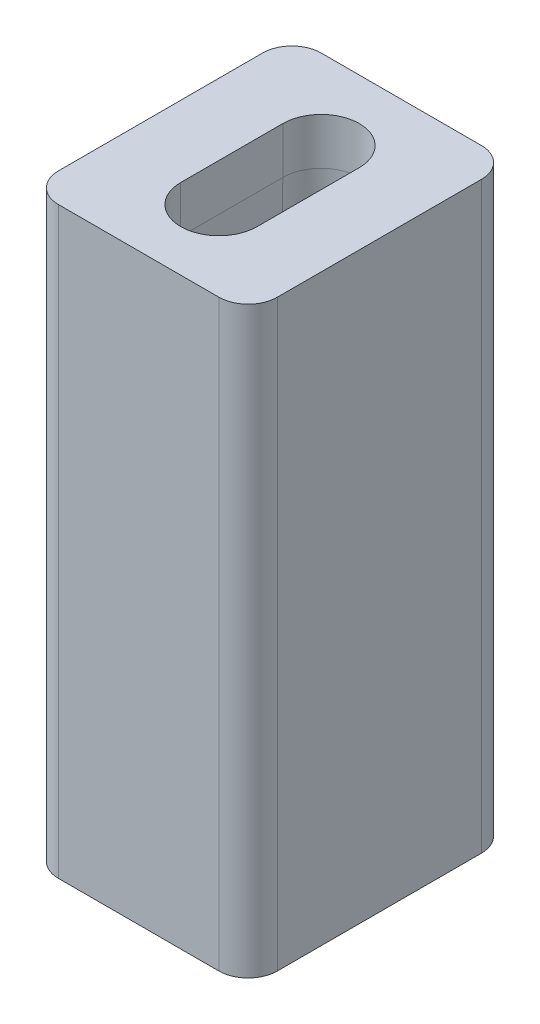
SolidWorks part; units mm, degrees
material "K110"
ref_plane "Front Plane" through (0, 0, 0) normal (0, 0, 1) x (1, 0, 0)
ref_plane "Top Plane" through (0, 0, 0) normal (0, 1, 0) x (1, 0, 0)
ref_plane "Right Plane" through (0, 0, 0) normal (1, 0, 0) x (0, 0, -1)
sketch "Sketch1" plane through (0, 0, 0) normal (0, 1, 0) x (1, 0, 0)
  line L3 (0, -3.5) -> (0, 3.5) construction
  line L4 (-2.62, -3.5) -> (-2.62, 3.5) construction
  line L5 (2.62, -3.5) -> (2.62, 3.5) construction
  line L6 (-5.5, -9) -> (5.5, -9)
  line L7 (-7.5, -7) -> (-7.5, 7)
  line L8 (-5.5, 9) -> (5.5, 9)
  line L9 (7.5, -7) -> (7.5, 7)
  line L10 (-7.5, -9) -> (7.5, 9) construction
  line L11 (-7.5, 9) -> (7.5, -9) construction
  arc A2 (-2.62, -3.5) -> (2.62, -3.5) centre (0, -3.5) ccw construction
  arc A3 (2.62, 3.5) -> (-2.62, 3.5) centre (0, 3.5) ccw construction
  arc A4 (-5.5, -9) -> (-7.5, -7) centre (-5.5, -7) cw
  arc A5 (5.5, -9) -> (7.5, -7) centre (5.5, -7) ccw
  arc A6 (5.5, 9) -> (7.5, 7) centre (5.5, 7) cw
  arc A7 (-7.5, 7) -> (-5.5, 9) centre (-5.5, 7) cw
  point P0 (0, 0)
  point P10 (0, 0)
  dimension "D1" = 7
  dimension "D3" = 2.62
  dimension "D5" = 2
  dimension "D2" = 18
  dimension "D4" = 15
extrude "Boss-Extrude1" add sketch "Sketch1" against normal blind 40
sketch "Sketch5" plane through (0, 0, 0) normal (0, 1, 0) x (1, 0, 0)
  line L0 (0, -3.5) -> (0, 3.5) construction
  line L1 (-2.62, -3.5) -> (-2.62, 3.5)
  line L2 (2.62, -3.5) -> (2.62, 3.5)
  arc A0 (-2.62, -3.5) -> (2.62, -3.5) centre (0, -3.5) ccw
  arc A1 (2.62, 3.5) -> (-2.62, 3.5) centre (0, 3.5) ccw
  point P4 (0, 0)
extrude "Cut-Extrude2" cut sketch "Sketch5" against normal up to next
sketch "Sketch7" plane through (0, 0, 0) normal (0, 0, 1) x (1, 0, 0)
  line L0 (2.62, -3.2) -> (3.2623, -40)
  line L1 (2.62, -40) -> (2.62, 0) construction
  line L2 (-5.5, -40) -> (5.5, -40) construction
  line L3 (3.2623, -40) -> (2.62, -40)
  line L4 (2.62, -40) -> (2.62, -3.2)
  line L5 (7.5, 0) -> (5.5, 0) construction
  dimension "D1" = 3.2
  dimension "D2" = 1
sketch "Sketch8" plane through (0, 0, 0) normal (0, 1, 0) x (1, 0, 0)
  line L0 (-2.62, 3.5) -> (-2.62, -3.5) construction
  line L1 (2.62, -3.5) -> (2.62, 3.5) construction
  line L2 (-2.62, 3.5) -> (-2.62, -3.5)
  line L3 (2.62, -3.5) -> (2.62, 3.5)
  arc A0 (2.62, 3.5) -> (-2.62, 3.5) centre (0, 3.5) ccw construction
  arc A1 (-2.62, -3.5) -> (2.62, -3.5) centre (0, -3.5) ccw construction
  arc A2 (2.62, 3.5) -> (-2.62, 3.5) centre (0, 3.5) ccw
  arc A3 (-2.62, -3.5) -> (2.62, -3.5) centre (0, -3.5) ccw
sweep "Cut-Sweep1" cut profiles "Sketch7" path "Sketch8"
hole_wizard "M3 Tapped Hole1" positions "Sketch11" profile "Sketch10" tap size "M3" standard "ISO"
sketch "Sketch11" plane through (0, -40, 0) normal (0, -1, 0) x (-1, 0, 0)
  line L0 (-5.5, 9) -> (5.5, 9) construction
  line L1 (-7.5, -7) -> (-7.5, 7) construction
  line L4 (7.5, 7) -> (7.5, -7) construction
  line L5 (5.5, -9) -> (-5.5, -9) construction
  point P0 (-5, 6.5)
  point P2 (5, -6.5)
  dimension "D1" = 2.5
  dimension "D2" = 2.5
  dimension "D3" = 2.5
  dimension "D4" = 2.5
sketch "Sketch10" plane through (5, -40, -6.5) normal (1, 0, 0) x (0, 0, -1)
  line L0 (0, 0) -> (0, 9.2511)
  line L1 (0, 9.2511) -> (1.25, 8.5)
  line L2 (1.25, 8.5) -> (1.25, 0.275)
  line L3 (1.25, 0.275) -> (1.525, 0)
  line L5 (1.525, 0) -> (0, 0)
  line L6 (-1.25, 0.275) -> (-1.525, 0) construction
  line L10 (0, 9.2511) -> (-1.25, 8.5) construction
  line L11 (0, -6.35) -> (0, 107.95) construction
  dimension "Tap Drill Dia." = 2.5
  dimension "Tap Drill Depth" = 8.5
  dimension "Near C'Sink Dia." = 3.05
  dimension "Near C'Sink Angle" = 90
  dimension "Drill Angle" = 118
cosmetic thread "Hole Thread1"
cosmetic thread "Hole Thread2"
